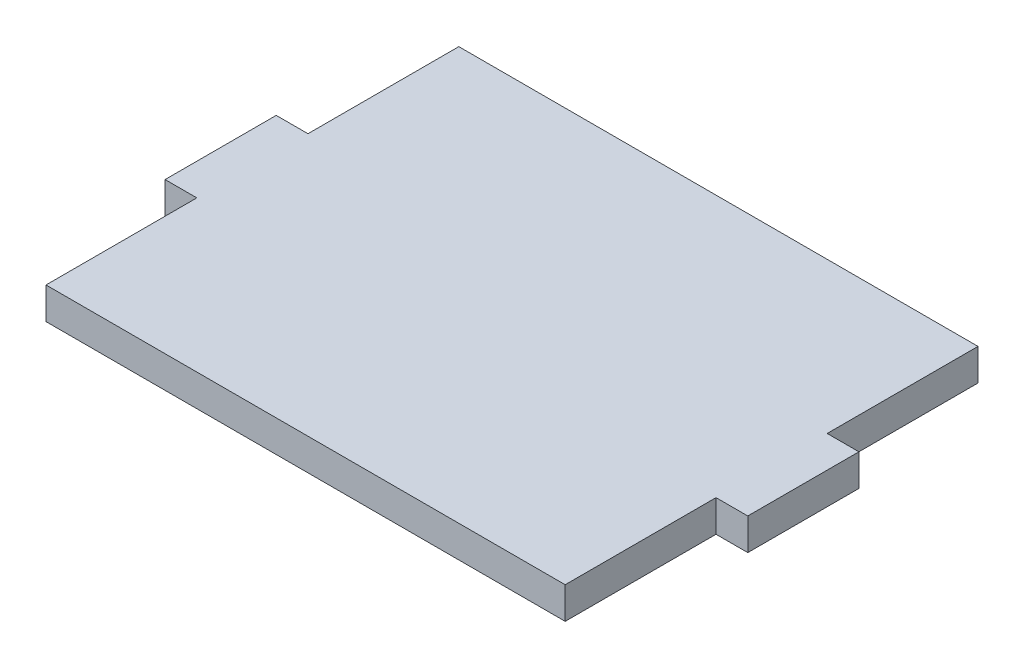
SolidWorks part; units mm, degrees
ref_plane "Front Plane" through (0, 0, 0) normal (0, 0, 1) x (1, 0, 0)
ref_plane "Top Plane" through (0, 0, 0) normal (0, 1, 0) x (1, 0, 0)
ref_plane "Right Plane" through (0, 0, 0) normal (1, 0, 0) x (0, 0, -1)
sketch "Sketch1" plane through (0, 0, 0) normal (0, 1, 0) x (1, 0, 0)
  line L1 (-16.35, 13) -> (16.35, 13)
  line L2 (-16.35, 13) -> (-16.35, -13)
  line L3 (-16.35, -13) -> (16.35, -13)
  line L4 (16.35, 13) -> (16.35, -13)
  line L5 (-16.35, 13) -> (16.35, -13) construction
  line L6 (-16.35, -13) -> (16.35, 13) construction
  line L7 (16.35, -3.5) -> (18.35, -3.5)
  line L8 (16.35, -3.5) -> (16.35, 3.5)
  line L9 (16.35, 3.5) -> (18.35, 3.5)
  line L10 (18.35, -3.5) -> (18.35, 3.5)
  line L11 (-16.35, 3.5) -> (-18.35, 3.5)
  line L12 (-16.35, 3.5) -> (-16.35, -3.5)
  line L13 (-16.35, -3.5) -> (-18.35, -3.5)
  line L14 (-18.35, 3.5) -> (-18.35, -3.5)
  point P0 (0, 0)
  dimension "D1" = 26
  dimension "D2" = 32.7
  dimension "D3" = 2
  dimension "D4" = 2
  dimension "D5" = 7
  dimension "D6" = 7
  dimension "D7" = 9.5
  dimension "D8" = 9.5
extrude "Boss-Extrude1" add sketch "Sketch1" along normal blind 2 contours L4 L1 L2 L3 | L11 L14 L13 L2 | L7 L10 L9 L4 region at (0, 0, 0) region at (-17.35, 0, 0) region at (17.35, 0, 0)
